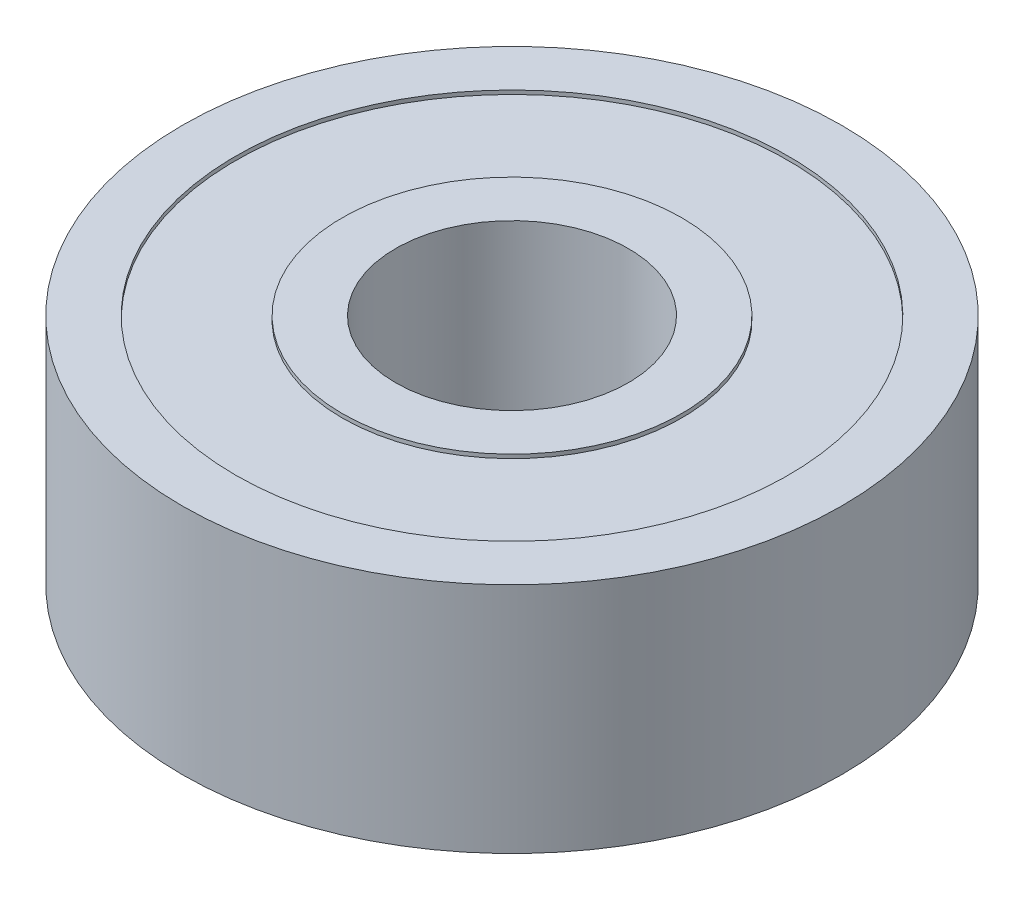
SolidWorks part; units mm, degrees
ref_plane "Front plane" through (0, 0, 0) normal (0, 0, 1) x (1, 0, 0)
ref_plane "Top plane" through (0, 0, 0) normal (0, 1, 0) x (1, 0, 0)
ref_plane "Right plane" through (0, 0, 0) normal (1, 0, 0) x (0, 0, -1)
ref_axis "Axis X" through (0, 0, 0) along (1, 0, 0)
ref_axis "Axis Y" through (0, 0, 0) along (0, 1, 0)
ref_axis "Axis Z" through (0, 0, 0) along (0, 0, 1)
sketch "Sketch1" plane through (0, 0, 0) normal (0, 1, 0) x (1, 0, 0)
  circle A0 centre (0, 0) radius 8.5
  circle A1 centre (0, 0) radius 3
  dimension "D1" = 17
  dimension "D2" = 6
extrude "Extrude1" add sketch "Sketch1" along normal blind 6
sketch "Sketch2" plane through (0, 6, 0) normal (0, 1, 0) x (1, 0, 0)
  circle A2 centre (0, 0) radius 7.125
  circle A3 centre (0, 0) radius 7.125
  circle A5 centre (0, 0) radius 4.375
  circle A6 centre (0, 0) radius 4.375
  dimension "D1" = 1.375
  dimension "D2" = 1.375
extrude "Extrude2" cut sketch "Sketch2" against normal blind 0.1
sketch "Sketch3" plane through (0, 0, 0) normal (0, -1, 0) x (1, 0, 0)
  circle A2 centre (0, 0) radius 7.125
  circle A3 centre (0, 0) radius 7.125
  circle A5 centre (0, 0) radius 4.375
  circle A6 centre (0, 0) radius 4.375
  dimension "D1" = 1.375
  dimension "D2" = 1.375
extrude "Extrude3" cut sketch "Sketch3" against normal blind 0.1
equation "\"motor_D\"= 30'Motor diameter"
equation "\"motor_H\"= 13'Motor heigh"
equation "\"motor_d1\"= 25.4558'Seating diameter of screws on the fixed part of the motor"
equation "\"motor_s1\"= 2'Screws diameter on the fixed part of motor"
equation "\"motor_a2\"= 10'Seating parameter in rectangle of screws on the moving part of the motor"
equation "\"motor_s2\"= 2'Screws diameter on the moving part of motor"
equation "\"motor_Dc\"= 5'Central hole diameter of motor"
equation "\"bearing_d1\"= 6'Bearing inner diameter"
equation "\"bearing_d2\"= 17'Bearing external diameter"
equation "\"bearing h\"= 6'Bearing heigh"
equation "\"pin_d\"= 2'Pin diameter"
equation "\"pin_h\"= 12'Pin heigh"
equation "\"magnet_d1\"= 5'Magnet inner diameter"
equation "\"magnet_d2\"= 9.5'Magnet external diameter"
equation "\"magnet_h\"= 3'Magnet heigh"
equation "\"motor_b2\"= 22'Seating parameter in rectangle of screws on the moving part of the motor"
equation "\"motor_d2\"= 0'Seating diameter of screws on the moving part of the motor (if this parameter is not determine, write 0)"
equation "\"motor_cmd\"= 12'Central magnet mount diameter"
equation "\"motor_cmh\"= 1.4'Central magnet mount heigh (if not write 0)"
equation "\"motor_whR\"= 10'Distance from center of motor to wires"
equation "\"D1@Sketch1\"=\"bearing_d2\""
equation "\"D2@Sketch1\"=\"bearing_d1\""
equation "\"D1@Extrude1\"=\"bearing h\""
equation "\"D1@Sketch2\"=(\"bearing_d2\"-\"bearing_d1\")/2/4"
equation "\"D2@Sketch2\"=\"D1@Sketch2\""
equation "\"D1@Extrude2\"=0.1"
equation "\"D2@Sketch3\"=(\"bearing_d2\"-\"bearing_d1\")/2/4"
equation "\"D1@Sketch3\"=\"D2@Sketch3\""
equation "\"print_offset\"= 0.2'Offset for printing holes"
equation "\"ft_sensor_d1\"= 9.8"
equation "\"ft_sensor_d2\"= 24.9"
equation "\"ft_sensor_d3\"= 22.6'Inner diameter of "
equation "\"ft_sensor_h\"= 7.1"
equation "\"ft_sensor_whD\"= 5"
